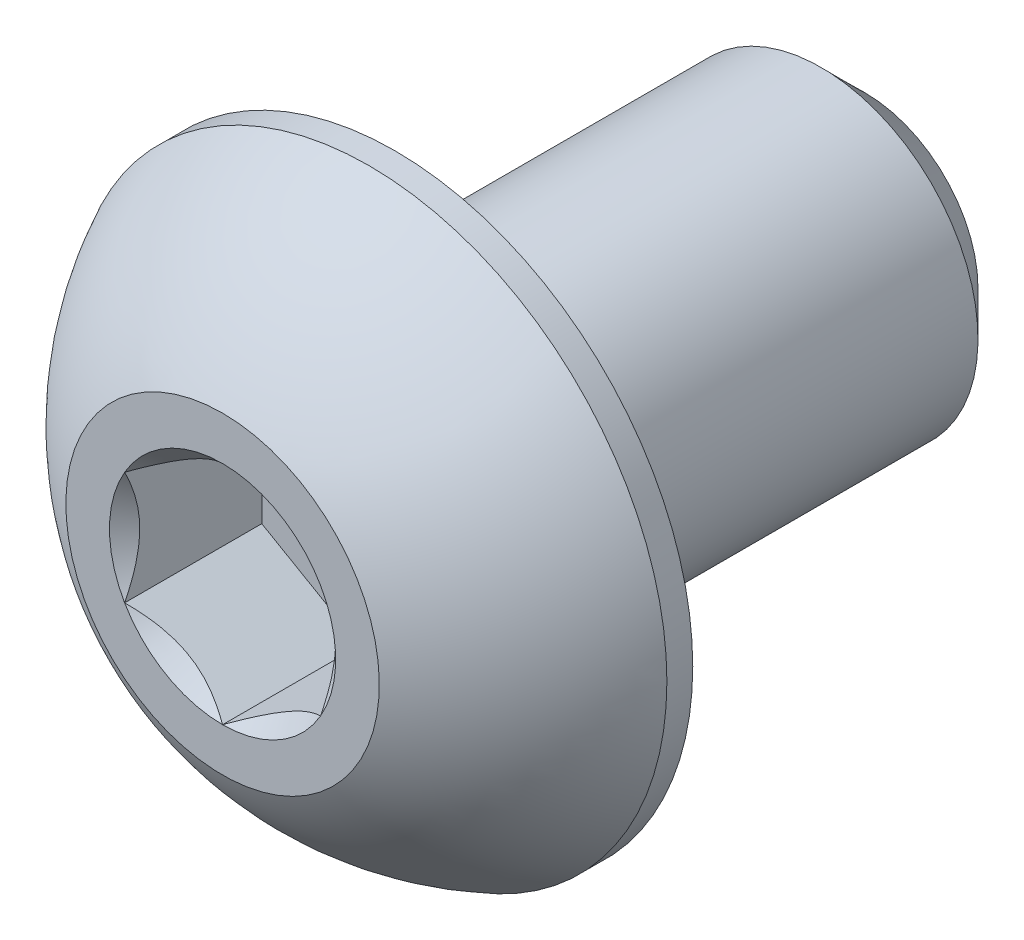
SolidWorks part; units mm, degrees
ref_plane "Front Plane" through (0, 0, 0) normal (0, 0, 1) x (1, 0, 0)
ref_plane "Top Plane" through (0, 0, 0) normal (0, 1, 0) x (1, 0, 0)
ref_plane "Right Plane" through (0, 0, 0) normal (1, 0, 0) x (0, 0, -1)
sketch "Sketch1" plane through (0, 0, 0) normal (1, 0, 0) x (0, 0, -1)
  line L0 (-4.1, 0) -> (4.1, 0) construction
  line L1 (-1.9, 3.8) -> (-1.9, -3.8) construction
  line L2 (4.1, 2) -> (4.1, -2) construction
  line L3 (4.0563, 2.0758) -> (4.4063, 1.4696) construction
  line L4 (4.4063, 1.4696) -> (4.7562, 2.0758) construction
  line L5 (4.7562, 2.0758) -> (4.0563, 2.0758) construction
  line L6 (4.1, 2) -> (4.7125, 2) construction
  line L7 (4.4062, 2.0758) -> (4.4062, 2) construction
  line L8 (4.4062, 2) -> (4.4062, 1.5453) construction
  line L9 (4.4062, 1.5453) -> (4.4063, 1.4696) construction
  line L10 (4.3625, 1.5453) -> (4.45, 1.5453)
  line L11 (4.0781, 2.0379) -> (4.7344, 2.0379)
  line L12 (4.45, 1.5453) -> (4.7344, 2.0379)
  line L13 (4.3625, 1.5453) -> (4.0781, 2.0379)
  line L14 (-4.1, 1.25) -> (-4.1, -1.25) construction
  line L15 (4.1, 2) -> (-1.9, 2) construction
  point P3 (-1.9, 0)
  point P6 (-2.35, 0)
  point P21 (4.4062, 2.0379)
  point P24 (-2.23, 3.8)
  point P25 (2.35, -2)
  point P26 (-4.1, 2)
  dimension "Head Height" = 2.2
  dimension "Length" = 6
  dimension "Head Dia" = 7.6
  dimension "Thread Dia" = 4
  dimension "Pitch" = 0.7
  dimension "D2" = 0.0875
  dimension "Drive Size" = 2.5
  dimension "D1" = 1.75
  dimension "D3" = 0.33
  dimension "D4" = 1.75
sketch "Sketch2" plane through (0, 0, 0) normal (1, 0, 0) x (0, 0, -1)
  line L0 (-4.1, 0) -> (4.1, 0)
  line L1 (4.1, 0) -> (4.1, 1.44)
  line L2 (4.1, 2) -> (4.1, -2) construction
  line L3 (4.1, 1.44) -> (3.54, 2)
  line L4 (3.54, 2) -> (-1.9, 2)
  line L5 (-1.9, 3.8) -> (-1.9, -3.8) construction
  line L6 (-1.9, 2) -> (-1.9, 3.8)
  line L7 (-1.9, 3.8) -> (-2.23, 3.8)
  line L8 (4.1, 2) -> (4.7125, 2) construction
  line L9 (-4.1, 0) -> (-4.1, 2)
  arc A0 (-4.1, 2) -> (-2.23, 3.8) centre (-0.3736, 0) cw
  dimension "D1" = 0.56
  dimension "D2" = 45
revolve "Revolve1" add sketch "Sketch2" angle 360 about L0
sketch "Sketch3" plane through (0, 0, 4.1) normal (0, 0, 1) x (1, 0, 0)
  line L1 (0, 1.4434) -> (-1.25, 0.7217)
  line L2 (-1.25, 0.7217) -> (-1.25, -0.7217)
  line L3 (-1.25, -0.7217) -> (0, -1.4434)
  line L4 (0, -1.4434) -> (1.25, -0.7217)
  line L5 (1.25, -0.7217) -> (1.25, 0.7217)
  line L6 (1.25, 0.7217) -> (0, 1.4434)
  circle A0 centre (0, 0) radius 1.25 construction
  dimension "D1" = 2.5
extrude "Cut-Extrude1" cut sketch "Sketch3" against normal up to vertex (1.75 mm away) up to point (0, 0, 2.35)
sketch "Sketch4" plane through (0, 0, 4.1) normal (0, 0, 1) x (1, 0, 0)
  circle A0 centre (0, 0) radius 1.4434
extrude "Cut-Extrude2" cut sketch "Sketch4" against normal blind 10 draft 45
split "Split1" [suppressed] bodies to split 106
sketch "Sketch5" [suppressed] plane through (0, 0, -4.1) normal (0, 0, -1) x (-1, 0, 0)
  circle A0 centre (0, 0) radius 2 construction
  circle A1 centre (0, 0) radius 2
curve "Helix/Spiral1" [suppressed] pitch 0.7 height 6.7 turns 9.5714
sketch "Sketch6" [suppressed] plane through (0, 0, 0) normal (1, 0, 0) x (0, 0, -1)
  line L0 (4.3625, 1.5453) -> (4.45, 1.5453) construction
  line L1 (4.3625, 1.5453) -> (4.0781, 2.0379) construction
  line L2 (4.0781, 2.0379) -> (4.7344, 2.0379) construction
  line L3 (4.45, 1.5453) -> (4.7344, 2.0379) construction
  line L4 (4.3625, 1.5453) -> (4.45, 1.5453)
  line L5 (4.3625, 1.5453) -> (4.0781, 2.0379)
  line L6 (4.0781, 2.0379) -> (4.7344, 2.0379)
  line L7 (4.45, 1.5453) -> (4.7344, 2.0379)
sweep "Cut-Sweep1" [suppressed] cut profiles "Sketch6" path "Helix/Spiral1"
sketch "Sketch7" [suppressed] plane through (0, 0, 1.9) normal (0, 0, -1) x (-1, 0, 0)
  circle A1 centre (0, 0) radius 2
  circle A2 centre (0, 0) radius 2
  dimension "D1" = 0
extrude "Boss-Extrude1" [suppressed] add sketch "Sketch7" along normal blind 10 draft 30
equation "\"D2@Sketch1\" = \"Pitch@Sketch1\" / 8"
equation "\"D1@Sketch1\"=\"Drive Size@Sketch1\"*.7"
equation "\"D3@Sketch1\"=\"Head Height@Sketch1\"*.15"
equation "\"D1@Sketch2\"=\"Pitch@Sketch1\"*.8"
equation "\"D1@Sketch3\"=\"Drive Size@Sketch1\""
equation "\"D4@Helix/Spiral1\"=\"Pitch@Sketch1\""
equation "\"D3@Helix/Spiral1\"=\"Length@Sketch1\"+\"Pitch@Sketch1\""
equation "\"D4@Sketch1\"=\"Pitch@Sketch1\"*2.5"
